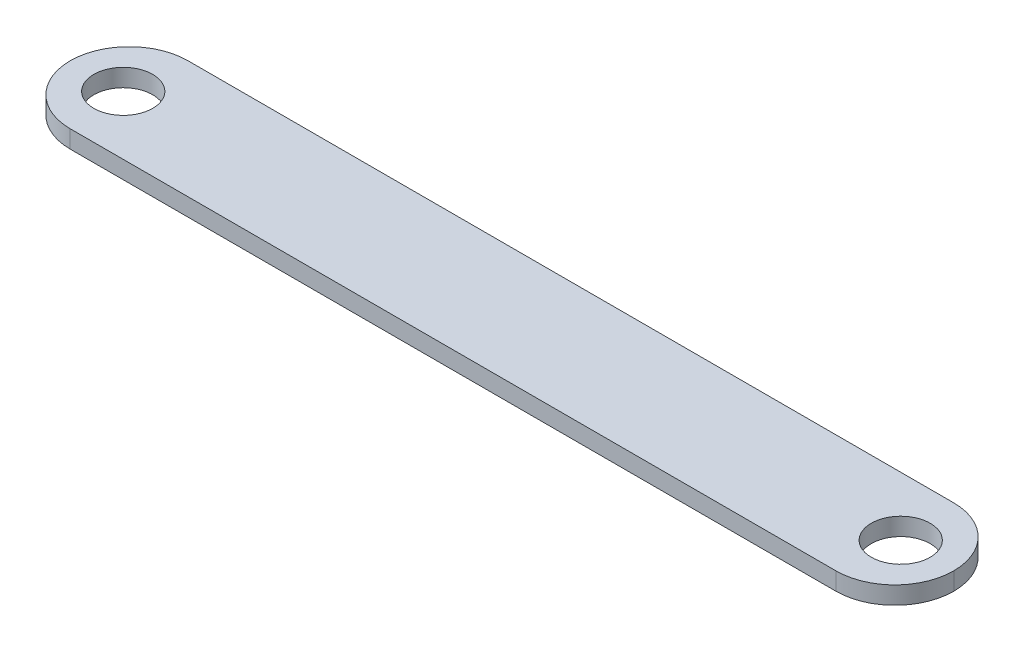
SolidWorks part; units mm, degrees
ref_plane "Front Plane" through (0, 0, 0) normal (0, 0, 1) x (1, 0, 0)
ref_plane "Top Plane" through (0, 0, 0) normal (0, 1, 0) x (1, 0, 0)
ref_plane "Right Plane" through (0, 0, 0) normal (1, 0, 0) x (0, 0, -1)
sketch "Sketch2" plane through (0, 0, 0) normal (0, 1, 0) x (1, 0, 0)
  line L1 (0, 0) -> (150, 0)
  line L2 (0, 0) -> (0, 20)
  line L3 (0, 20) -> (150, 20)
  line L4 (150, 0) -> (150, 20)
  dimension "D1" = 150
  dimension "D2" = 20
extrude "Boss-Extrude1" add sketch "Sketch2" along normal blind 3
sketch "Sketch3" plane through (0, 3, 0) normal (0, 1, 0) x (1, 0, 0)
  line L0 (150, 20) -> (0, 20) construction
  line L1 (0, 20) -> (0, 0) construction
  circle A0 centre (9, 10) radius 5
  dimension "D1" = 10
  dimension "D2" = 9
extrude "Cut-Extrude1" cut sketch "Sketch3" against normal through all
sketch "Sketch4" plane through (0, 3, 0) normal (0, 1, 0) x (1, 0, 0)
  line L0 (150, 20) -> (0, 20) construction
  line L1 (150, 0) -> (150, 20) construction
  circle A0 centre (141, 10) radius 5
  dimension "D1" = 10
  dimension "D2" = 9
extrude "Cut-Extrude2" cut sketch "Sketch4" against normal through all
fillet "Fillet1" radius 10 2 edges at (0, 1.5, -20) (0, 1.5, 0)
fillet "Fillet2" radius 10 2 edges at (150, 1.5, -20) (150, 1.5, 0)
